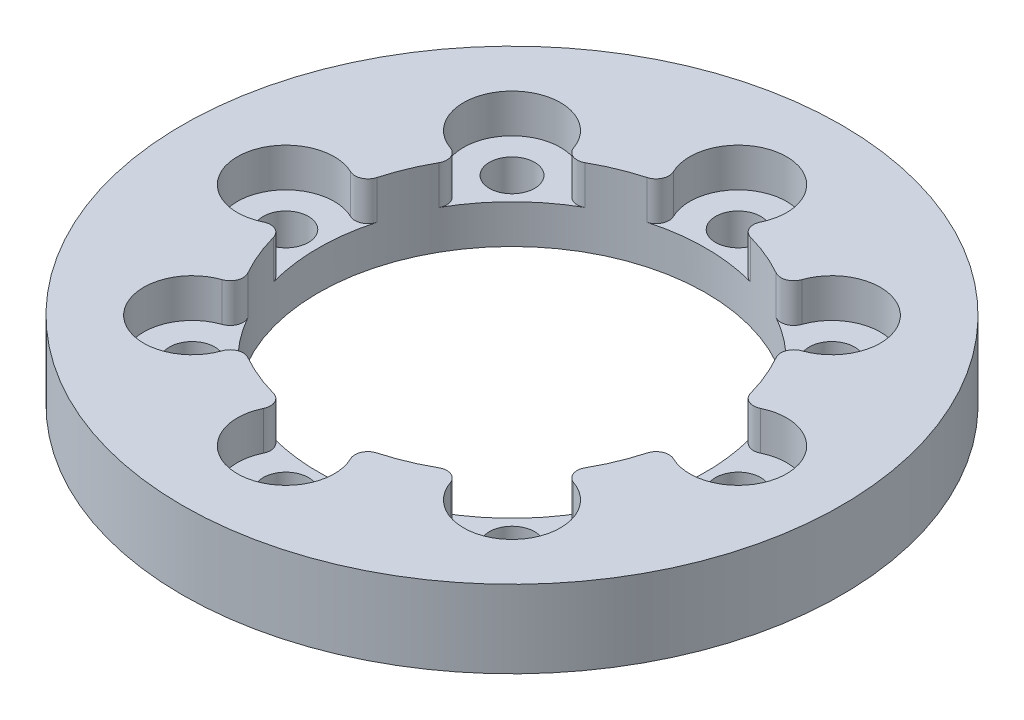
SolidWorks part; units mm, degrees
ref_plane "Front Plane" through (0, 0, 0) normal (0, 0, 1) x (1, 0, 0)
ref_plane "Top Plane" through (0, 0, 0) normal (0, 1, 0) x (1, 0, 0)
ref_plane "Right Plane" through (0, 0, 0) normal (1, 0, 0) x (0, 0, -1)
sketch "Sketch1" plane through (0, 0, 0) normal (0, 1, 0) x (1, 0, 0)
  circle A0 centre (0, 0) radius 25.5
  circle A1 centre (0, 0) radius 15
  circle A2 centre (0, 17.5) radius 1.75
  circle A3 centre (12.3744, 12.3744) radius 1.75
  circle A4 centre (17.5, 0) radius 1.75
  circle A5 centre (12.3744, -12.3744) radius 1.75
  circle A6 centre (0, -17.5) radius 1.75
  circle A7 centre (-12.3744, -12.3744) radius 1.75
  circle A8 centre (-17.5, 0) radius 1.75
  circle A9 centre (-12.3744, 12.3744) radius 1.75
  point P22 (0, 0)
  dimension "D1" = 30
  dimension "D2" = 51
  dimension "D4" = 3.5
  dimension "D3" = 17.5
  dimension "D5" = 8
extrude "Boss-Extrude1" add sketch "Sketch1" along normal blind 6
sketch "Sketch2" plane through (0, 6, 0) normal (0, 1, 0) x (1, 0, 0)
  circle A0 centre (-12.3744, 12.3744) radius 3.75
  circle A1 centre (-12.3744, 12.3744) radius 1.75
  circle A2 centre (-12.3744, 12.3744) radius 1.75
  circle A3 centre (-12.3744, -12.3744) radius 1.75
  circle A4 centre (-12.3744, -12.3744) radius 1.75
  circle A5 centre (12.3744, -12.3744) radius 1.75
  circle A6 centre (12.3744, -12.3744) radius 1.75
  circle A7 centre (12.3744, 12.3744) radius 1.75
  circle A8 centre (12.3744, 12.3744) radius 1.75
  circle A9 centre (0, 17.5) radius 1.75
  circle A10 centre (0, 17.5) radius 1.75
  circle A11 centre (17.5, 0) radius 1.75
  circle A12 centre (17.5, 0) radius 1.75
  circle A13 centre (0, -17.5) radius 1.75
  circle A14 centre (0, -17.5) radius 1.75
  circle A15 centre (-17.5, 0) radius 1.75
  circle A16 centre (-17.5, 0) radius 1.75
  circle A17 centre (-12.3744, -12.3744) radius 3.75
  circle A18 centre (12.3744, -12.3744) radius 3.75
  circle A19 centre (12.3744, 12.3744) radius 3.75
  circle A20 centre (0, 17.5) radius 3.75
  circle A21 centre (17.5, 0) radius 3.75
  circle A22 centre (0, -17.5) radius 3.75
  circle A23 centre (-17.5, 0) radius 3.75
  dimension "D1" = 0
  dimension "D2" = 0
  dimension "D3" = 0
  dimension "D4" = 0
  dimension "D5" = 0
  dimension "D6" = 0
  dimension "D7" = 0
  dimension "D8" = 0
  dimension "D9" = 2
extrude "Cut-Extrude1" cut sketch "Sketch2" against normal blind 3
fillet "Fillet1" radius 1 16 edges at (8.6258, 4.5, -12.2718) (-14.7768, 4.5, -2.5781) (-2.5781, 4.5, -14.7768) (2.5781, 4.5, -14.7768) (12.2718, 4.5, -8.6258) (14.7768, 4.5, -2.5781) (14.7768, 4.5, 2.5781) (12.2718, 4.5, 8.6258) (8.6258, 4.5, 12.2718) (-8.6258, 4.5, -12.2718) (-12.2718, 4.5, -8.6258) (2.5781, 4.5, 14.7768) (-2.5781, 4.5, 14.7768) (-14.7768, 4.5, 2.5781) (-8.6258, 4.5, 12.2718) (-12.2718, 4.5, 8.6258)
